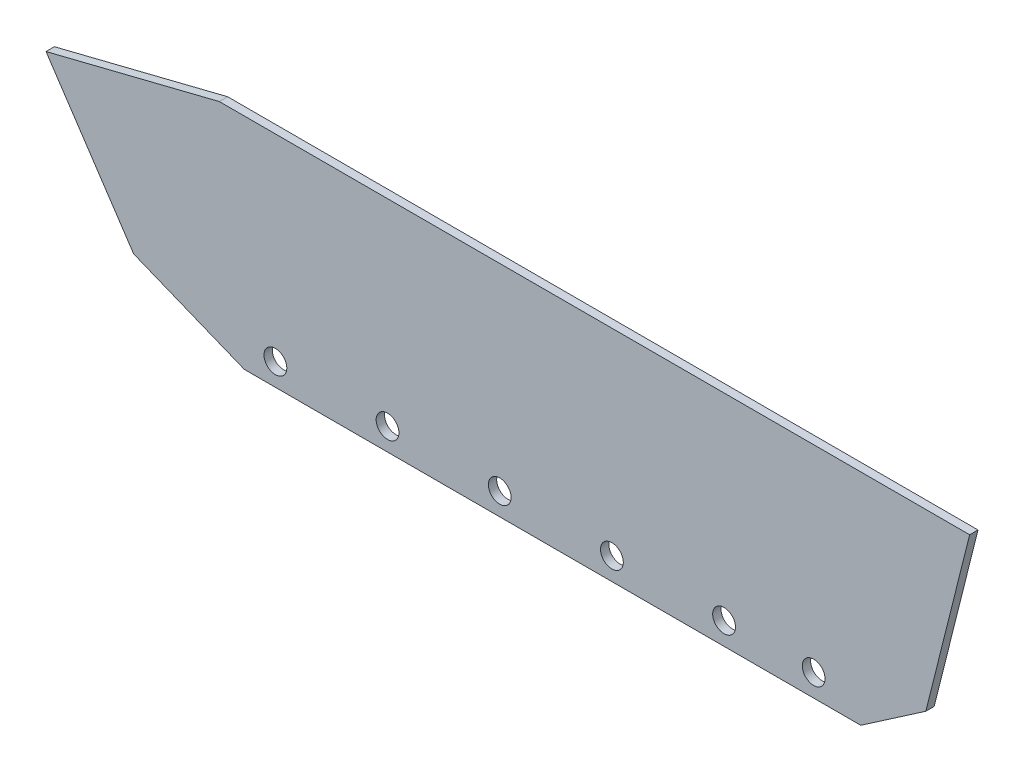
SolidWorks part; units mm, degrees
material "5052-H32"
ref_plane "Front Plane" through (0, 0, 0) normal (0, 0, 1) x (1, 0, 0)
ref_plane "Top Plane" through (0, 0, 0) normal (0, 1, 0) x (1, 0, 0)
ref_plane "Right Plane" through (0, 0, 0) normal (1, 0, 0) x (0, 0, -1)
sketch "Sketch1" plane through (0, 0, 0) normal (0, 0, 1) x (1, 0, 0)
  line L1 (428.1206, 33.3333) -> (428.1206, 28.5708)
  line L3 (428.1206, 28.5708) -> (0, 28.5708)
  line L4 (0, 28.5708) -> (-98.8794, 3.851)
  line L6 (-98.8794, 3.851) -> (-31.8794, -96.649)
  line L7 (428.1206, 28.5708) -> (403.1206, -71.149)
  line L9 (403.1206, -71.149) -> (366, -96.649)
  line L10 (-31.8794, -96.649) -> (366, -96.649)
  circle A0 centre (32, -83.899) radius 6.5
  circle A1 centre (96, -83.899) radius 6.5
  circle A2 centre (160, -83.899) radius 6.5
  circle A3 centre (224, -83.899) radius 6.5
  circle A4 centre (288, -83.899) radius 6.5
  circle A5 centre (339.1206, -83.899) radius 6.5
  point P0 (-48.8794, -71.149)
  point P2 (-31.8794, -96.649)
  point P8 (48, -83.899)
  point P9 (403.1206, -71.149)
  point P23 (0, 0)
  point P24 (0, 0)
  dimension "D2" = 16
  dimension "D4" = 64
  dimension "D1" = 25.5
  dimension "D3" = 75
  dimension "D5" = 25
  dimension "D6" = 64
  dimension "D7" = 527
  dimension "D9" = 64
  dimension "D10" = 64
  dimension "D11" = 64
  dimension "D12" = 123.69
  dimension "D13" = 12.75
extrude "Boss-Extrude1" add sketch "Sketch1" along normal blind 4.7625 contours L3 L4 L6 L10 L9 L7
extrude "Cut-Extrude1" cut sketch "Sketch1<4>" along normal through all contours A0 | A1 | A2 | A3 | A4 | A5 region at (32, -83.899, 0)
sketch "Sketch1<4>" plane through (0, 0, 0) normal (0, 0, 1) x (1, 0, 0) same geometry as "Sketch1"
sketch "Sketch2" plane through (0, 0, 0) normal (0, 0, -1) x (-1, 0, 0)
  circle A0 centre (-307.1206, -83.899) radius 6.5
  circle A2 centre (-249.5603, -111.8778) radius 6.5
  circle A3 centre (-192, -83.899) radius 6.5
  circle A4 centre (-128, -83.899) radius 6.5
  circle A5 centre (-64, -83.899) radius 6.5
  circle A6 centre (0, -83.899) radius 6.5
  dimension "D2" = 0
  dimension "D3" = 64
  dimension "D4" = 64
  dimension "D5" = 64
  dimension "D6" = 64
  dimension "D7" = 64
  dimension "D1" = 32
sketch "Sketch5" plane through (0, 0, 0) normal (0, 0, -1) x (-1, 0, 0)
  line L0 (48.8794, -71.149) -> (-14.2353, -96.649)
  line L1 (31.8794, -96.649) -> (-366, -96.649) construction
  line L2 (-14.2353, -96.649) -> (31.8794, -96.649)
  line L3 (31.8794, -96.649) -> (48.8794, -71.149)
  line L6 (-366, -96.649) -> (-403.1206, -71.149)
  line L7 (-403.1206, -71.149) -> (-352, -71.149)
  line L9 (-352, -71.149) -> (-326.5, -96.649)
  line L11 (-366, -96.649) -> (-326.5, -96.649)
  dimension "D1" = 22
  dimension "D2" = 45
extrude "Cut-Extrude2" [suppressed] cut sketch "Sketch5" against normal up to next
sketch "Sketch6" plane through (0, 0, 4.7625) normal (0, 0, 1) x (1, 0, 0)
  line L0 (-48.8794, -71.149) -> (14.2353, -96.649)
  line L1 (-31.8794, -96.649) -> (366, -96.649) construction
  line L2 (14.2353, -96.649) -> (-31.8794, -96.649)
  line L3 (-31.8794, -96.649) -> (-48.8794, -71.149)
  dimension "D1" = 158
extrude "Cut-Extrude3" cut sketch "Sketch6" against normal blind 10
